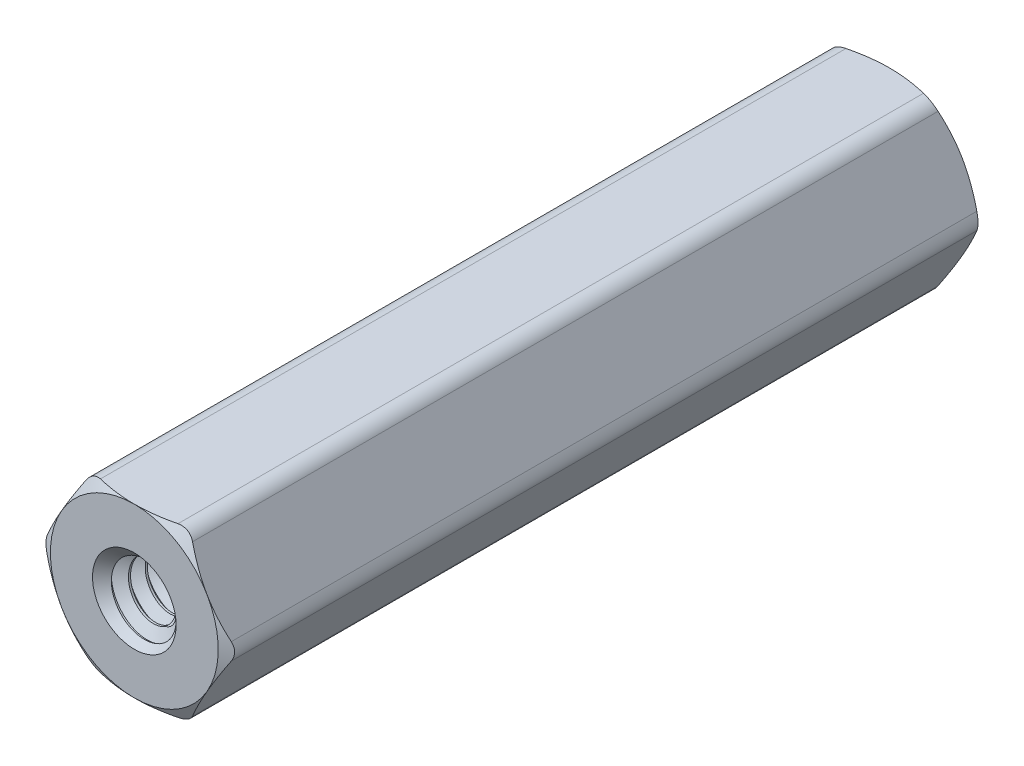
SolidWorks part; units mm, degrees
ref_plane "Front Plane" through (0, 0, 0) normal (0, 0, 1) x (1, 0, 0)
ref_plane "Top Plane" through (0, 0, 0) normal (0, 1, 0) x (1, 0, 0)
ref_plane "Right Plane" through (0, 0, 0) normal (1, 0, 0) x (0, 0, -1)
sketch "Sketch1" plane through (0, 0, 0) normal (0, 0, 1) x (1, 0, 0)
  line L0 (0, 0) -> (3.6662, 0) construction
  line L1 (1.8331, -3.175) -> (3.6662, 0)
  line L2 (3.6662, 0) -> (1.8331, 3.175)
  line L3 (1.8331, 3.175) -> (-1.8331, 3.175)
  line L4 (-1.8331, 3.175) -> (-3.6662, 0)
  line L5 (-3.6662, 0) -> (-1.8331, -3.175)
  line L6 (-1.8331, -3.175) -> (1.8331, -3.175)
  circle A0 centre (0, 0) radius 3.175 construction
  point P10 (0, -3.175)
  dimension "Hex Size" = 6.35
sketch "Sketch2" plane through (0, 0, 0) normal (1, 0, 0) x (0, 0, -1)
  line L0 (-7.9375, 0) -> (-14.2875, 0) construction
  line L3 (-7.9375, 1.4224) -> (-7.9375, -1.4224) construction
  line L4 (-14.8828, 1.4911) -> (-14.5653, 0.9412) construction
  line L5 (-14.5653, 0.9412) -> (-14.2478, 1.4911) construction
  line L6 (-14.2478, 1.4911) -> (-14.8828, 1.4911) construction
  line L7 (-14.8431, 1.4224) -> (-14.2875, 1.4224) construction
  line L8 (-14.605, 1.01) -> (-14.5256, 1.01) construction
  line L9 (-14.5653, 1.01) -> (-14.5653, 0.9412) construction
  line L10 (-14.5653, 1.4224) -> (-14.5653, 1.4911) construction
  line L11 (14.2875, 3.175) -> (-14.2875, 3.175) construction
  point P6 (0, 3.175)
  point P9 (-7.9375, 0)
  dimension "Minimum Thread Length" = 6.35
  dimension "Thread Size" = 2.8448
  dimension "Thread Pitch" = 0.635
  dimension "Thread Pitch (B)/8" = 0.0794
  dimension "Length" = 28.575
sketch "Sketch3" plane through (0, 0, 0) normal (1, 0, 0) x (0, 0, -1)
  line L1 (-7.9375, 1.4224) -> (-7.9375, 0)
  line L2 (14.2875, 3.175) -> (14.2875, 1.4224)
  line L6 (14.2875, 3.175) -> (14.2875, 1.4224)
  line L8 (14.2875, 1.4224) -> (7.9375, 1.4224)
  line L9 (-14.1288, 1.4224) -> (-14.2875, 1.5812)
  line L10 (0, 3.175) -> (14.2875, 3.175)
  line L11 (-14.2875, 1.5812) -> (-14.2875, 3.175)
  line L12 (-14.2875, 3.175) -> (0, 3.175)
  line L13 (-7.9375, 0) -> (7.9375, 0)
  line L14 (7.9375, 0) -> (7.9375, 1.4224)
  line L16 (-7.9375, 1.4224) -> (-14.1288, 1.4224)
  point P5 (-14.2875, -3.175)
  dimension "D1" = 45
  dimension "D3" = 0.1588
revolve "Revolve1" add sketch "Sketch3" angle 360 about L0
sketch "Sketch4" plane through (0, 0, 0) normal (0, 0, 1) x (1, 0, 0)
  line L0 (0, 3.175) -> (0, 1.4224) construction
  line L1 (-1.8331, 3.175) -> (-3.6662, 0)
  line L2 (-3.6662, 0) -> (-1.8331, -3.175)
  line L3 (-1.8331, -3.175) -> (1.8331, -3.175)
  line L4 (1.8331, -3.175) -> (3.6662, 0)
  line L5 (3.6662, 0) -> (1.8331, 3.175)
  line L6 (1.8331, 3.175) -> (-1.8331, 3.175)
  line L7 (1.8331, -3.175) -> (3.6662, 0) construction
  circle A0 centre (0, 0) radius 3.175 construction
  circle A1 centre (0, 0) radius 2.2987
  circle A2 centre (0, 0) radius 3.175 construction
  point P16 (0, 2.2987)
extrude "Boss-Extrude1" add sketch "Sketch4" against normal mid plane 28.575
sketch "Sketch5" plane through (0, 0, 14.2875) normal (0, 0, 1) x (1, 0, 0)
  line L0 (0, 1.4224) -> (0, -1.4224) construction
  line L1 (0, 1.4224) -> (0, -1.4224) construction
  circle A0 centre (0, 0) radius 3.175
  circle A1 centre (0, 0) radius 3.175 construction
  point P11 (0, -1.4224)
extrude "Cut-Extrude1" cut sketch "Sketch5" against normal through all draft 60 flip side to cut
sketch "Sketch6" plane through (0, 0, -14.2875) normal (0, 0, -1) x (-1, 0, 0)
  circle A0 centre (0, 0) radius 3.175
  circle A1 centre (0, 0) radius 3.175 construction
extrude "Cut-Extrude2" cut sketch "Sketch6" against normal through all draft 60 flip side to cut
fillet "Fillet1" radius 0.635 6 edges at (1.8331, 3.175, 0) (-3.6662, 0, 0) (-1.8331, -3.175, 0) (1.8331, -3.175, 0) (3.6662, 0, 0) (-1.8331, 3.175, 0)
sketch "Drawing 1" plane through (0, 0, 0) normal (1, 0, 0) x (0, 0, -1)
  line L0 (-7.9375, -1.4224) -> (-14.2875, -1.4224) construction
  line L1 (-7.9375, 1.4224) -> (-14.2875, 1.4224) construction
  line L2 (14.2875, 1.4224) -> (7.9375, 1.4224) construction
  line L3 (-7.9375, 0) -> (-14.2875, 0) construction
  line L4 (7.9375, 1.4224) -> (7.9375, -1.4224) construction
  line L5 (7.9375, -1.4224) -> (14.2875, -1.4224) construction
  line L6 (-7.9375, 1.4224) -> (-7.9375, -1.4224) construction
split "Split1" trim tools "Front Plane" bodies to split 107 resulting bodies 120
sketch "Sketch7" plane through (0, 0, 7.9375) normal (0, 0, -1) x (-1, 0, 0)
  circle A0 centre (0, 0) radius 1.5812
extrude "Boss-Extrude2" add sketch "Sketch7" along normal up to surface (6.35 mm away)
sketch "Sketch8" plane through (0, 0, 0) normal (1, 0, 0) x (0, 0, -1)
  line L0 (-7.9375, 0) -> (-14.2875, 0) construction
  line L1 (-7.9375, 1.4224) -> (-14.2875, 1.4224)
  line L2 (-7.9375, 1.4224) -> (-7.9375, 0)
  line L3 (-7.9375, 0) -> (-14.2875, 0)
  line L4 (-14.2875, 1.4224) -> (-14.2875, 0)
revolve "Revolve2" add sketch "Sketch8" angle 360 about L0
sketch "Sketch9" plane through (0, 0, 14.2875) normal (0, 0, 1) x (1, 0, 0)
  circle A0 centre (0, 0) radius 1.4224
  circle A1 centre (0, 0) radius 1.4224 construction
sketch "Sketch10" plane through (0, 0, 0) normal (1, 0, 0) x (0, 0, -1)
  line L0 (-14.605, 1.01) -> (-14.5256, 1.01)
  line L1 (-14.5256, 1.01) -> (-14.2677, 1.4568)
  line L2 (-14.5653, 0.9412) -> (-14.2478, 1.4911) construction
  line L3 (-14.2677, 1.4568) -> (-14.863, 1.4568)
  line L4 (-14.8828, 1.4911) -> (-14.5653, 0.9412) construction
  line L5 (-14.863, 1.4568) -> (-14.605, 1.01)
  line L6 (-14.5653, 1.4224) -> (-14.5653, 1.4911) construction
  point P12 (-14.5653, 1.4568)
curve "Helix/Spiral1" pitch 0.635 height 6.985 turns 11
sweep "Cut-Sweep1" cut profiles "Sketch10" path "Helix/Spiral1"
combine bodies "Combine1" operation type subtract main body 113 bodies to subtract 114
ref_plane "Plane1" through (0, 0, 14.1288) normal (0, 0, 1) x (1, 0, 0)
sketch "Sketch11" plane through (0, 0, 14.2875) normal (0, 0, 1) x (1, 0, 0)
  circle A0 centre (0, 0) radius 1.5811
extrude "Cut-Extrude3" cut sketch "Sketch11" against normal through all draft 45
pattern_circular "CirPattern1" count 2 over 360 about axis through (0, 0, 0) along (1, 0, 0) of bodies 116 118
combine bodies "Combine2" bodies to combine 116 121
equation "\"Thread Pitch (B)/8@Sketch2\" = \"Thread Pitch@Sketch2\" / 8"
equation "\"D1@Fillet1\" = \"Hex Size@Sketch1\" * .1"
equation "\"D3@Helix/Spiral1\" = \"Minimum Thread Length@Sketch2\" + \"Thread Pitch@Sketch2\""
equation "\"D4@Helix/Spiral1\" = \"Thread Pitch@Sketch2\""
equation "\"D1@Boss-Extrude1\" = \"Length@Sketch2\""
equation "\"D3@Sketch3\"=\"Thread Pitch@Sketch2\"*.25"
